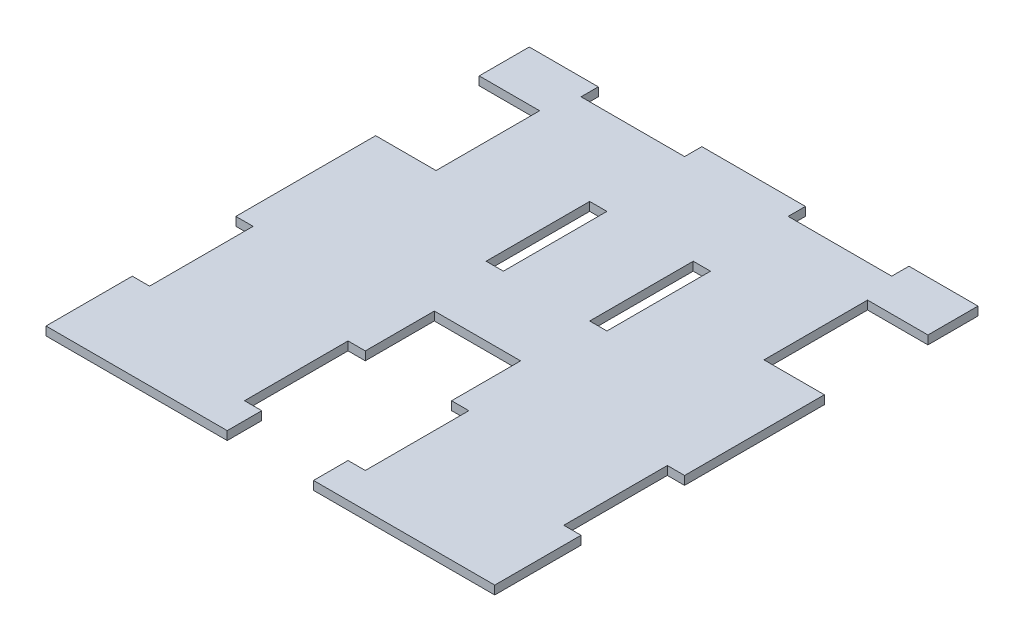
SolidWorks part; units mm, degrees
ref_plane "Front Plane" through (0, 0, 0) normal (0, 0, 1) x (1, 0, 0)
ref_plane "Top Plane" through (0, 0, 0) normal (0, 1, 0) x (1, 0, 0)
ref_plane "Right Plane" through (0, 0, 0) normal (1, 0, 0) x (0, 0, -1)
sketch "Sketch1" plane through (0, 0, 0) normal (0, 1, 0) x (1, 0, 0)
  line L1 (-165.1, -177.8) -> (165.1, -177.8)
  line L2 (-165.1, -177.8) -> (-165.1, 177.8)
  line L3 (-165.1, 177.8) -> (165.1, 177.8)
  line L4 (165.1, -177.8) -> (165.1, 177.8)
  line L5 (-165.1, -177.8) -> (165.1, 177.8) construction
  line L6 (-165.1, 177.8) -> (165.1, -177.8) construction
  point P0 (0, 0)
  dimension "D1" = 355.6
  dimension "D2" = 330.2
extrude "Boss-Extrude1" add sketch "Sketch1" along normal blind 6.35
sketch "Sketch2" plane through (0, 6.35, 0) normal (0, 1, 0) x (1, 0, 0)
  line L0 (-165.1, -177.8) -> (165.1, -177.8) construction
  line L1 (-31.75, -25.4) -> (31.75, -25.4)
  line L2 (-31.75, -25.4) -> (-31.75, -177.8)
  line L3 (-31.75, -177.8) -> (31.75, -177.8)
  line L4 (31.75, -25.4) -> (31.75, -177.8)
  line L5 (-31.75, -25.4) -> (31.75, -177.8) construction
  line L6 (-31.75, -177.8) -> (31.75, -25.4) construction
  point P0 (0, -101.6)
  dimension "D1" = 152.4
  dimension "D2" = 63.5
extrude "Cut-Extrude1" cut sketch "Sketch2" against normal through all
sketch "Sketch3" plane through (0, 6.35, 0) normal (0, 1, 0) x (1, 0, 0)
  line L1 (120.65, 140.97) -> (165.1, 140.97)
  line L2 (120.65, 140.97) -> (120.65, 64.77)
  line L3 (120.65, 64.77) -> (165.1, 64.77)
  line L4 (165.1, 140.97) -> (165.1, 64.77)
  line L6 (0, -3.4925) -> (0, 3.4925) construction
  line L7 (-120.65, 64.77) -> (-165.1, 64.77)
  line L8 (-165.1, 140.97) -> (-165.1, 64.77)
  line L9 (-120.65, 140.97) -> (-165.1, 140.97)
  line L10 (-120.65, 140.97) -> (-120.65, 64.77)
  line L12 (165.1, -177.8) -> (165.1, 177.8) construction
  line L14 (165.1, 177.8) -> (-165.1, 177.8) construction
  dimension "D1" = 76.2
  dimension "D2" = 44.45
  dimension "D3" = 36.83
extrude "Cut-Extrude2" cut sketch "Sketch3" against normal through all
sketch "Sketch4" plane through (0, 6.35, 0) normal (0, 1, 0) x (1, 0, 0)
  line L0 (-165.1, 177.8) -> (-165.1, 140.97) construction
  line L1 (-165.1, 140.97) -> (-152.4, 140.97)
  line L2 (-165.1, 140.97) -> (-165.1, 64.77)
  line L3 (-165.1, 64.77) -> (-152.4, 64.77)
  line L4 (-152.4, 140.97) -> (-152.4, 64.77)
  line L5 (0, -3.4925) -> (0, 3.4925) construction
  line L6 (-165.1, -114.3) -> (-152.4, -114.3)
  line L7 (-165.1, -114.3) -> (-165.1, -38.1)
  line L8 (-165.1, -38.1) -> (-152.4, -38.1)
  line L9 (-152.4, -114.3) -> (-152.4, -38.1)
  line L10 (165.1, 64.77) -> (152.4, 64.77)
  line L11 (152.4, 140.97) -> (152.4, 64.77)
  line L12 (165.1, 140.97) -> (152.4, 140.97)
  line L13 (165.1, 140.97) -> (165.1, 64.77)
  line L14 (165.1, -38.1) -> (152.4, -38.1)
  line L15 (152.4, -114.3) -> (152.4, -38.1)
  line L16 (165.1, -114.3) -> (152.4, -114.3)
  line L17 (165.1, -114.3) -> (165.1, -38.1)
  line L18 (165.1, 177.8) -> (-165.1, 177.8) construction
  line L19 (114.3, 165.1) -> (38.1, 165.1)
  line L20 (-114.3, 177.8) -> (-38.1, 177.8)
  line L21 (-114.3, 177.8) -> (-114.3, 165.1)
  line L22 (-114.3, 165.1) -> (-38.1, 165.1)
  line L23 (-38.1, 177.8) -> (-38.1, 165.1)
  line L24 (38.1, 177.8) -> (38.1, 165.1)
  line L25 (114.3, 177.8) -> (38.1, 177.8)
  line L26 (114.3, 177.8) -> (114.3, 165.1)
  line L27 (-31.75, -25.4) -> (-31.75, -177.8) construction
  line L28 (-31.75, -152.4) -> (-44.45, -152.4)
  line L29 (-31.75, -152.4) -> (-31.75, -76.2)
  line L30 (-31.75, -76.2) -> (-44.45, -76.2)
  line L31 (-44.45, -152.4) -> (-44.45, -76.2)
  line L32 (-165.1, -177.8) -> (-31.75, -177.8) construction
  line L33 (31.75, 101.6) -> (44.45, 101.6)
  line L34 (-31.75, 25.4) -> (-44.45, 25.4)
  line L35 (-31.75, 25.4) -> (-31.75, 101.6)
  line L36 (-31.75, 101.6) -> (-44.45, 101.6)
  line L37 (-44.45, 25.4) -> (-44.45, 101.6)
  line L38 (44.45, 25.4) -> (44.45, 101.6)
  line L39 (31.75, 25.4) -> (44.45, 25.4)
  line L40 (31.75, 25.4) -> (31.75, 101.6)
  line L41 (31.75, -76.2) -> (44.45, -76.2)
  line L42 (44.45, -152.4) -> (44.45, -76.2)
  line L43 (31.75, -152.4) -> (44.45, -152.4)
  line L44 (31.75, -152.4) -> (31.75, -76.2)
  dimension "D1" = 12.7
  dimension "D2" = 12.7
  dimension "D3" = 76.2
  dimension "D4" = 76.2
  dimension "D5" = 36.83
  dimension "D6" = 215.9
  dimension "D7" = 12.7
  dimension "D8" = 76.2
  dimension "D9" = 76.2
  dimension "D10" = 12.7
  dimension "D11" = 76.2
  dimension "D12" = 25.4
  dimension "D13" = 76.2
  dimension "D14" = 12.7
  dimension "D15" = 203.2
extrude "Cut-Extrude3" cut sketch "Sketch4" against normal through all
